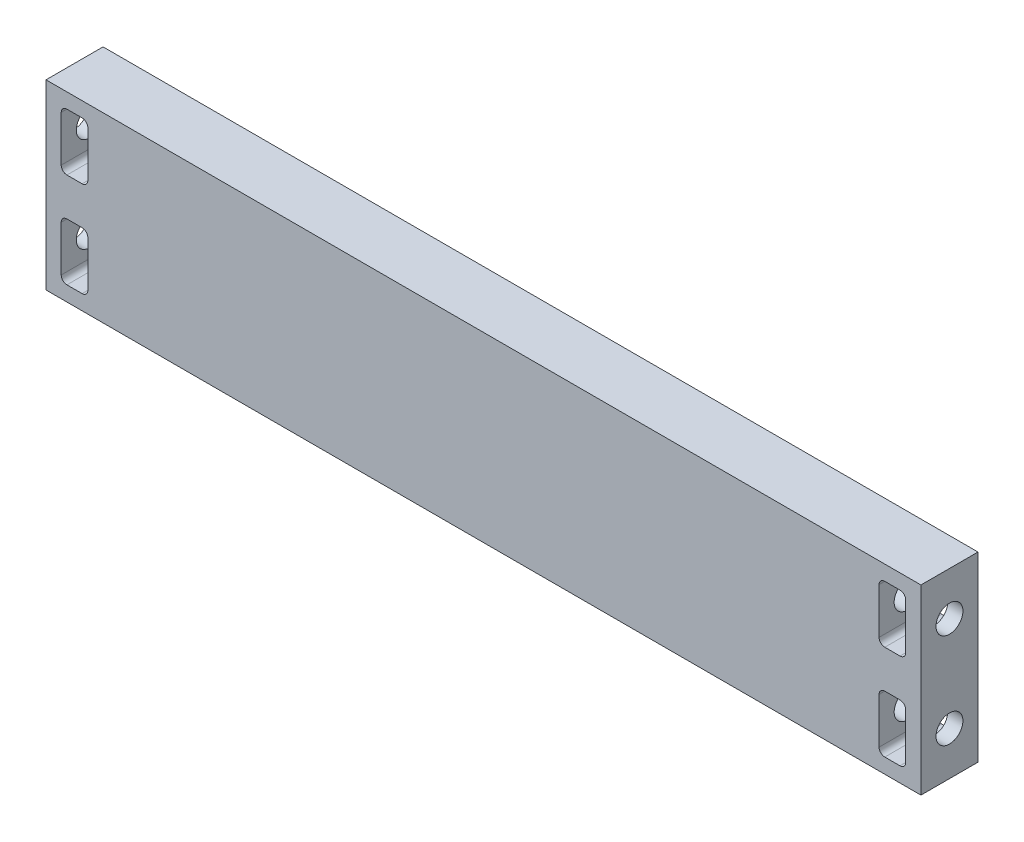
SolidWorks part; units mm, degrees
material "PE High Density"
ref_plane "Front Plane" through (0, 0, 0) normal (0, 0, 1) x (1, 0, 0)
ref_plane "Top Plane" through (0, 0, 0) normal (0, 1, 0) x (1, 0, 0)
ref_plane "Right Plane" through (0, 0, 0) normal (1, 0, 0) x (0, 0, -1)
sketch "Sketch1" plane through (0, 0, 0) normal (0, 0, 1) x (1, 0, 0)
  line L0 (-69.5325, 12.7) -> (-66.9925, 12.7)
  line L1 (-73.025, 15.1929) -> (73.025, 15.1929)
  line L2 (-73.025, 15.1929) -> (-73.025, -15.1929)
  line L3 (-73.025, -15.1929) -> (73.025, -15.1929)
  line L4 (73.025, 15.1929) -> (73.025, -15.1929)
  line L5 (-73.025, 15.1929) -> (73.025, -15.1929) construction
  line L6 (-73.025, -15.1929) -> (73.025, 15.1929) construction
  line L7 (-70.485, 11.7475) -> (-70.485, 4.1275)
  line L8 (-69.5325, 3.175) -> (-66.9925, 3.175)
  line L9 (-66.04, 11.7475) -> (-66.04, 4.1275)
  line L10 (-70.485, 12.7) -> (-66.04, 3.175) construction
  line L11 (-70.485, 3.175) -> (-66.04, 12.7) construction
  line L12 (-68.2625, 15.875) -> (-68.2625, -15.875) construction
  line L13 (-68.2625, 3.175) -> (-68.2625, 11.967) construction
  line L14 (-70.485, 7.9375) -> (-66.04, 7.9375) construction
  line L15 (-73.025, 0) -> (73.025, 0) construction
  line L16 (0, -15.1929) -> (0, 15.1929) construction
  line L17 (-70.485, -7.9375) -> (-66.04, -7.9375) construction
  line L18 (-68.2625, -3.175) -> (-68.2625, -11.967) construction
  line L19 (-70.485, -3.175) -> (-66.04, -12.7) construction
  line L20 (-70.485, -12.7) -> (-66.04, -3.175) construction
  line L21 (-66.04, -11.7475) -> (-66.04, -4.1275)
  line L22 (-69.5325, -3.175) -> (-66.9925, -3.175)
  line L23 (-70.485, -11.7475) -> (-70.485, -4.1275)
  line L24 (-69.5325, -12.7) -> (-66.9925, -12.7)
  line L25 (70.485, 7.9375) -> (66.04, 7.9375) construction
  line L26 (68.2625, 3.175) -> (68.2625, 11.967) construction
  line L27 (70.485, 3.175) -> (66.04, 12.7) construction
  line L28 (70.485, 12.7) -> (66.04, 3.175) construction
  line L29 (66.04, 11.7475) -> (66.04, 4.1275)
  line L30 (69.5325, 3.175) -> (66.9925, 3.175)
  line L31 (70.485, 11.7475) -> (70.485, 4.1275)
  line L32 (69.5325, 12.7) -> (66.9925, 12.7)
  line L33 (70.485, -12.7) -> (66.04, -3.175) construction
  line L34 (70.485, -3.175) -> (66.04, -12.7) construction
  line L35 (68.2625, -3.175) -> (68.2625, -11.967) construction
  line L36 (70.485, -7.9375) -> (66.04, -7.9375) construction
  line L37 (69.5325, -12.7) -> (66.9925, -12.7)
  line L38 (70.485, -11.7475) -> (70.485, -4.1275)
  line L39 (69.5325, -3.175) -> (66.9925, -3.175)
  line L40 (66.04, -11.7475) -> (66.04, -4.1275)
  arc A0 (-66.9925, 3.175) -> (-66.04, 4.1275) centre (-66.9925, 4.1275) ccw
  arc A1 (-66.9925, 12.7) -> (-66.04, 11.7475) centre (-66.9925, 11.7475) cw
  arc A2 (-69.5325, 3.175) -> (-70.485, 4.1275) centre (-69.5325, 4.1275) cw
  arc A3 (-69.5325, 12.7) -> (-70.485, 11.7475) centre (-69.5325, 11.7475) ccw
  arc A4 (-69.5325, -12.7) -> (-70.485, -11.7475) centre (-69.5325, -11.7475) cw
  arc A5 (-69.5325, -3.175) -> (-70.485, -4.1275) centre (-69.5325, -4.1275) ccw
  arc A6 (-66.9925, -12.7) -> (-66.04, -11.7475) centre (-66.9925, -11.7475) ccw
  arc A7 (-66.9925, -3.175) -> (-66.04, -4.1275) centre (-66.9925, -4.1275) cw
  arc A8 (69.5325, 12.7) -> (70.485, 11.7475) centre (69.5325, 11.7475) cw
  arc A9 (69.5325, 3.175) -> (70.485, 4.1275) centre (69.5325, 4.1275) ccw
  arc A10 (66.9925, 12.7) -> (66.04, 11.7475) centre (66.9925, 11.7475) ccw
  arc A11 (66.9925, 3.175) -> (66.04, 4.1275) centre (66.9925, 4.1275) cw
  arc A12 (66.9925, -3.175) -> (66.04, -4.1275) centre (66.9925, -4.1275) ccw
  arc A13 (66.9925, -12.7) -> (66.04, -11.7475) centre (66.9925, -11.7475) cw
  arc A14 (69.5325, -3.175) -> (70.485, -4.1275) centre (69.5325, -4.1275) cw
  arc A15 (69.5325, -12.7) -> (70.485, -11.7475) centre (69.5325, -11.7475) ccw
  point P0 (0, 0)
  point P6 (-68.2625, 7.9375)
  point P53 (-68.2625, -7.9375)
  point P74 (68.2625, 7.9375)
  point P95 (68.2625, -7.9375)
  dimension "D5" = 0.9525
  dimension "D6" = 0.9525
  dimension "D7" = 0.9525
  dimension "D8" = 0.9525
  dimension "D1" = 146.05
  dimension "D2" = 30.3858
  dimension "D3" = 4.445
  dimension "D4" = 9.525
  dimension "D9" = 4.7625
  dimension "D10" = 7.9375
extrude "Boss-Extrude1" add sketch "Sketch1" along normal blind 9.525
sketch "Sketch2" plane through (73.025, 0, 0) normal (1, 0, 0) x (0, 0, -1)
  line L0 (-4.7625, 15.1929) -> (-4.7625, -15.1929) construction
  line L1 (-9.525, 15.1929) -> (0, 15.1929) construction
  line L2 (-9.525, -15.1929) -> (0, -15.1929) construction
  line L3 (-9.525, 0) -> (0, 0) construction
  line L4 (-9.525, -15.1929) -> (-9.525, 15.1929) construction
  circle A0 centre (-4.7625, 7.9375) radius 2.2479
  dimension "D1" = 4.4958
  dimension "D2" = 7.9375
extrude "Cut-Extrude1" cut sketch "Sketch2" against normal blind 10.795
mirror "Mirror1" about plane through (0, 0, 0) normal (1, 0, 0) of "Cut-Extrude1" second plane through (0, 0, 0) second plane normal (0, 1, 0)
equation "\"Plate Width\" = 3.5in"
equation "\"Plate Thickness\" = 0.375in"
equation "\"Num holes\" = 4"
equation "\"Plate Height\" = 1.25in"
equation "\"Top Plate Width\" = 4.5in"
equation "\"Plate Clearance Hole Diameter\" = 0.125in"
equation "\"Plate Tap Hole Diameter\" = 0.116in"
equation "\"Bottom Plate Length\" = 6.5in"
equation "\"Number Eight Clearance Size\" = 0.177in"
equation "\"D1@Sketch1\"=\"Bottom Plate Length\" - \"Plate Thickness\" * 2"
equation "\"D2@Sketch1\"=\"Back Brace Height\""
equation "\"D9@Sketch1\"=\"Plate Thickness\"/2"
equation "\"D10@Sketch1\"=\"Plate Height\"/4"
equation "\"D1@Boss-Extrude1\"=\"Plate Thickness\""
equation "\"D1@Sketch2\"=\"Number Eight Clearance Size\""
equation "\"D2@Sketch2\"=\"Plate Height\"/4"
equation "\"D1@Cut-Extrude1\"=0.8 - \"Plate Thickness\""
equation "\"Back Brace Height\" = 1.1962912in"
